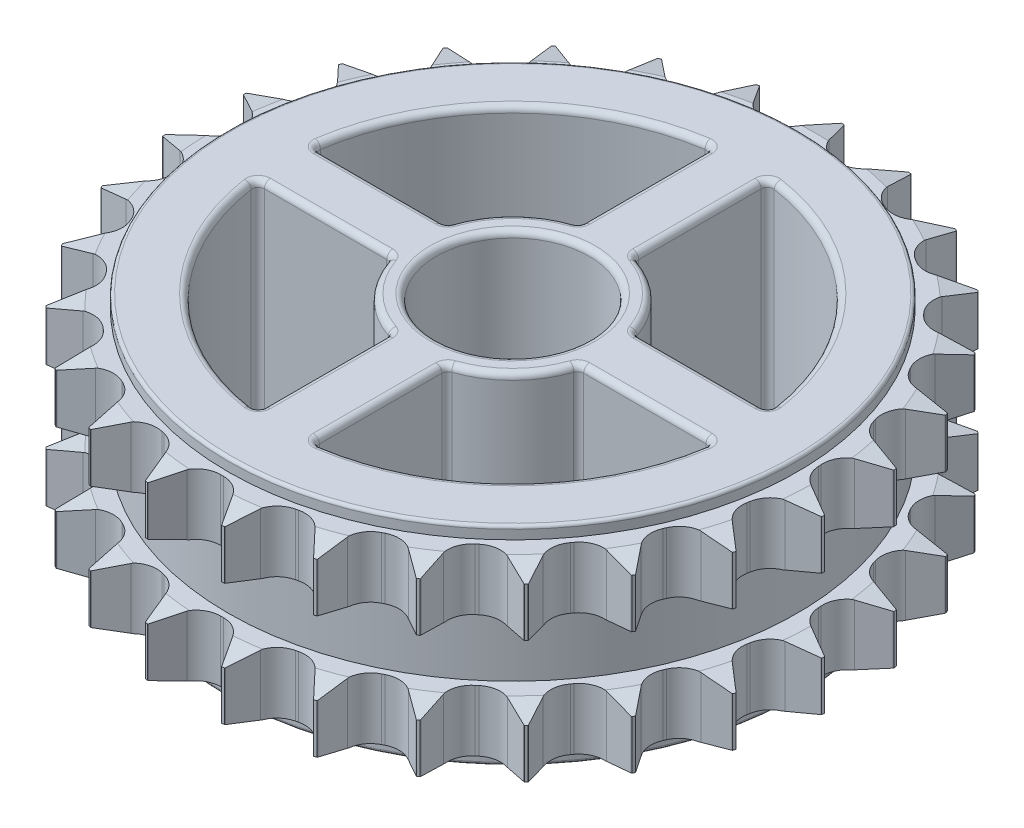
SolidWorks part; units mm, degrees
ref_plane "Front Plane" through (0, 0, 0) normal (0, 0, 1) x (1, 0, 0)
ref_plane "Top Plane" through (0, 0, 0) normal (0, 1, 0) x (1, 0, 0)
ref_plane "Right Plane" through (0, 0, 0) normal (1, 0, 0) x (0, 0, -1)
sketch "Sketch1" plane through (0, 0, 0) normal (0, 1, 0) x (1, 0, 0)
  line L0 (3, 47.4052) -> (0, 54.5)
  line L1 (0, 54.5) -> (-3, 47.4052)
  line L2 (0, 54.5) -> (0, 47.5) construction
  line L3 (-3, 47.4052) -> (0, 47.5) construction
  line L4 (0, 47.5) -> (3, 47.4052) construction
  line L5 (-3, 47.4052) -> (0, 47.5) construction
  line L6 (0, 47.5) -> (3, 47.4052) construction
  line L7 (13.8515, 45.4355) -> (12.5686, 53.0309)
  line L8 (12.5686, 53.0309) -> (8.0132, 46.8192)
  line L9 (23.9563, 41.0164) -> (24.4596, 48.703)
  line L10 (24.4596, 48.703) -> (18.5945, 43.7092)
  line L11 (32.7696, 34.3861) -> (35.0319, 41.7494)
  line L12 (35.0319, 41.7494) -> (28.1733, 38.2428)
  line L13 (39.8163, 25.902) -> (43.7157, 32.5451)
  line L14 (43.7157, 32.5451) -> (36.2333, 30.7148)
  line L15 (44.7164, 16.0216) -> (50.0428, 21.5863)
  line L16 (50.0428, 21.5863) -> (42.3399, 21.5309)
  line L17 (47.2059, 5.2774) -> (53.672, 9.4638)
  line L18 (53.672, 9.4638) -> (46.164, 11.1862)
  line L19 (47.1505, -5.7513) -> (54.4078, -3.1689)
  line L20 (54.4078, -3.1689) -> (47.4994, 0.2386)
  line L21 (44.5532, -16.4699) -> (52.2104, -15.6308)
  line L22 (52.2104, -15.6308) -> (46.2741, -10.722)
  line L23 (39.5541, -26.3007) -> (47.1984, -27.25)
  line L24 (47.1984, -27.25) -> (42.5541, -21.1045)
  line L25 (32.4225, -34.7135) -> (39.6419, -37.4002)
  line L26 (39.6419, -37.4002) -> (36.54, -30.3493)
  line L27 (23.5431, -41.255) -> (29.9482, -45.5341)
  line L28 (29.9482, -45.5341) -> (28.556, -37.9579)
  line L29 (13.3944, -45.5723) -> (18.6401, -51.2132)
  line L30 (18.6401, -51.2132) -> (19.0326, -43.5202)
  line L31 (2.5237, -47.4329) -> (6.3271, -54.1315)
  line L32 (6.3271, -54.1315) -> (8.4831, -46.7364)
  line L33 (-8.4831, -46.7364) -> (-6.3271, -54.1315)
  line L34 (-6.3271, -54.1315) -> (-2.5237, -47.4329)
  line L35 (-19.0326, -43.5202) -> (-18.6401, -51.2132)
  line L36 (-18.6401, -51.2132) -> (-13.3944, -45.5723)
  line L37 (-28.556, -37.9579) -> (-29.9482, -45.5341)
  line L38 (-29.9482, -45.5341) -> (-23.5431, -41.255)
  line L39 (-36.54, -30.3493) -> (-39.6419, -37.4002)
  line L40 (-39.6419, -37.4002) -> (-32.4225, -34.7135)
  line L41 (-42.5541, -21.1045) -> (-47.1984, -27.25)
  line L42 (-47.1984, -27.25) -> (-39.5541, -26.3007)
  line L43 (-46.2741, -10.722) -> (-52.2104, -15.6308)
  line L44 (-52.2104, -15.6308) -> (-44.5532, -16.4699)
  line L45 (-47.4994, 0.2386) -> (-54.4078, -3.1689)
  line L46 (-54.4078, -3.1689) -> (-47.1505, -5.7513)
  line L47 (-46.164, 11.1862) -> (-53.672, 9.4638)
  line L48 (-53.672, 9.4638) -> (-47.2059, 5.2774)
  line L49 (-42.3399, 21.5309) -> (-50.0428, 21.5863)
  line L50 (-50.0428, 21.5863) -> (-44.7164, 16.0216)
  line L51 (-36.2333, 30.7148) -> (-43.7157, 32.5451)
  line L52 (-43.7157, 32.5451) -> (-39.8163, 25.902)
  line L53 (-28.1733, 38.2428) -> (-35.0319, 41.7494)
  line L54 (-35.0319, 41.7494) -> (-32.7696, 34.3861)
  line L55 (-18.5945, 43.7092) -> (-24.4596, 48.703)
  line L56 (-24.4596, 48.703) -> (-23.9563, 41.0164)
  line L57 (-8.0132, 46.8192) -> (-12.5686, 53.0309)
  line L58 (-12.5686, 53.0309) -> (-13.8515, 45.4355)
  line L59 (0, 16) -> (0, 37.5) construction
  line L60 (-4.5, 37.229) -> (-4.5, 15.3542)
  line L61 (4.5, 37.229) -> (4.5, 15.3542)
  line L62 (37.229, -4.5) -> (15.3542, -4.5)
  line L63 (37.229, 4.5) -> (15.3542, 4.5)
  line L64 (-4.5, -37.229) -> (-4.5, -15.3542)
  line L65 (4.5, -37.229) -> (4.5, -15.3542)
  line L66 (-37.229, 4.5) -> (-15.3542, 4.5)
  line L67 (-37.229, -4.5) -> (-15.3542, -4.5)
  line L69 (-1.7, 1.3964) -> (-1.7, -1.3964)
  circle A0 centre (0, 0) radius 47.5
  circle A1 centre (0, 0) radius 37.5
  circle A2 centre (0, 0) radius 5
  circle A3 centre (0, 0) radius 2.2
  circle A4 centre (0, 0) radius 16
  circle A5 centre (0, 0) radius 46.5
  point P88 (0, 0)
  point P111 (0, 0)
  dimension "D1" = 95
  dimension "D5" = 75
  dimension "D6" = 10
  dimension "D7" = 4.4
  dimension "D8" = 32
  dimension "D9" = 4
  dimension "D11" = 0.5
  dimension "D12" = 1
  dimension "D2" = 7
  dimension "D3" = 3
  dimension "D10" = 9
  dimension "D4" = 27
extrude "Boss-Extrude2" add sketch "Sketch1" along normal blind 10 from offset 2 contours A2 A3 | L69 A3 | A4 A2 | A4 L62 A1 L63 | A4 L64 A1 L65 | A4 L66 A1 L67 | A4 L61 A1 L60 | A5 A1 | A0 | L69 A3 region at (5.4988, 0, -47.0454) region at (0, 0, -26.5974) region at (0, 0, -15.5475) region at (-26.5974, 0, 0) region at (26.5974, 0, 0) region at (0, 0, 26.5974) region at (0.1274, 0, 0) region at (-1.9021, 0, 0) region at (-4.8586, 0, 0) region at (-45.1848, 0, 0)
extrude "Boss-Extrude3" add sketch "Sketch1<7>" along normal blind 22 contours L69 A3 | A5 A1 | A4 A2 | A2 A3 | A4 L66 A1 L67 | A4 L64 A1 L65 | A4 L62 A1 L63 | A4 L61 A1 L60 | A3 region at (0, 0, -26.5974) region at (0, 0, -15.5475) region at (-26.5974, 0, 0) region at (26.5974, 0, 0) region at (0, 0, 26.5974) region at (-1.9021, 0, 0) region at (-4.8586, 0, 0) region at (-45.1848, 0, 0)
sketch "Sketch1<7>" plane through (0, 0, 0) normal (0, 1, 0) x (1, 0, 0) same geometry as "Sketch1"
extrude "Boss-Extrude4" add sketch "Sketch1<8>" along normal blind 10 from surface contours A4 A2 | A2 A3 | L69 A3 | A4 L62 A1 L63 | A4 L64 A1 L65 | A4 L66 A1 L67 | A4 L61 A1 L60 | A5 A1 | A0 region at (5.4988, 0, -47.0454) region at (0, 0, -26.5974) region at (0, 0, -15.5475) region at (-26.5974, 0, 0) region at (26.5974, 0, 0) region at (0, 0, 26.5974) region at (-1.9021, 0, 0) region at (-4.8586, 0, 0) region at (-45.1848, 0, 0) starting at face at (-17.1554, 22, 17.1554)
sketch "Sketch1<8>" plane through (0, 0, 0) normal (0, 1, 0) x (1, 0, 0) same geometry as "Sketch1"
extrude "Boss-Extrude6" add sketch "Sketch1<10>" along normal blind 10 from offset 2 contours A0 L57 L58 region at (-11.4875, 0, -48.4696)
sketch "Sketch1<10>" plane through (0, 0, 0) normal (0, 1, 0) x (1, 0, 0) same geometry as "Sketch1"
extrude "Boss-Extrude7" add sketch "Sketch1<12>" along normal blind 10 from surface contours A0 L57 L58 region at (-11.4875, 0, -48.4696) starting at face at (0, 22, 47.5)
sketch "Sketch1<12>" plane through (0, 0, 0) normal (0, 1, 0) x (1, 0, 0) same geometry as "Sketch1"
fillet "Fillet1" radius 4 4 edges at (-13.8515, 7, -45.4355) (-8.0132, 7, -46.8192) (-13.8515, 27, -45.4355) (-8.0132, 27, -46.8192)
fillet "Fillet2" radius 0.3 2 edges at (-12.5686, 7, -53.0309) (-12.5686, 27, -53.0309)
pattern_circular "CirPattern1" count 27 over 360 about axis through (0, 32, 0) along (0, 1, 0) of "Fillet2", "Fillet1", "Boss-Extrude7", "Boss-Extrude6"
sketch "Sketch3" plane through (0, 32, 0) normal (0, 1, 0) x (1, 0, 0)
  circle A0 centre (0, 0) radius 2.5
sketch "Sketch4" plane through (0, 32, 0) normal (0, 1, 0) x (1, 0, 0)
  circle A0 centre (0, 0) radius 0.5
  dimension "D1" = 1
sketch "Sketch6" plane through (0, 32, 0) normal (0, 1, 0) x (1, 0, 0)
  line L0 (-15.3542, 4.5) -> (-37.229, 4.5)
  line L1 (-15.3542, -4.5) -> (-37.229, -4.5)
  line L2 (4.5, 15.3542) -> (4.5, 37.229)
  line L3 (-4.5, 15.3542) -> (-4.5, 37.229)
  line L4 (15.3542, -4.5) -> (37.229, -4.5)
  line L5 (15.3542, 4.5) -> (37.229, 4.5)
  line L6 (-4.5, -15.3542) -> (-4.5, -37.229)
  line L7 (4.5, -15.3542) -> (4.5, -37.229)
  circle A0 centre (0, 0) radius 16
  circle A1 centre (0, 0) radius 46.5
  circle A2 centre (0, 0) radius 37.5
  circle A3 centre (0, 0) radius 16
  circle A4 centre (0, 0) radius 16
  circle A5 centre (0, 0) radius 16
  point P31 (0, 0)
  dimension "D1" = 93
  dimension "D2" = 32
  dimension "D3" = 4
extrude "Boss-Extrude12" add sketch "Sketch6" along normal blind 2 contours L2 A2 L3 A0 | A1 A2 | L0 A2 L1 A0 | L6 A2 L7 A0 | A0 | L4 A2 L5 A0 region at (-26.5974, 32, 0) region at (0, 32, 0) region at (0, 32, -26.5974) region at (0, 32, 26.5974) region at (26.5974, 32, 0) region at (-45.1848, 32, 0)
fillet "Fillet9" radius 0.5 2 edges at (0, 34, 46.5) (0, 0, 46.5)
sketch "Sketch7" plane through (0, 34, 0) normal (0, 1, 0) x (1, 0, 0)
  line L0 (0, 0) -> (0, 5.8384) construction
  line L1 (0, 0) -> (-4.8311, 0) construction
  circle A1 centre (-8, 0) radius 1.5
  circle A2 centre (0, 8) radius 1.5
  circle A3 centre (8, 0) radius 1.5
  circle A4 centre (0, -8) radius 1.5
  point P3 (0, 0)
  point P18 (0, 0)
  dimension "D2" = 3
  dimension "D1" = 90
  dimension "D3" = 8
  dimension "D4" = 4
extrude "Cut-Extrude1" cut sketch "Sketch7" against normal up to next
sketch "Sketch10" plane through (0, 34, 0) normal (0, 1, 0) x (1, 0, 0)
  circle A0 centre (0, 0) radius 12.5
  dimension "D1" = 25
extrude "Cut-Extrude2" cut sketch "Sketch10" against normal offset from surface (21 mm away) 13 up to face at (-8, 0, 1.5)
fillet "Fillet17" radius 1 44 edges at (15.3542, 17, -4.5) (37.229, 17, -4.5) (-4.5, 17, 37.229) (-4.5, 17, 15.3542) (-15.3542, 17, 4.5) (-37.229, 17, 4.5) (-37.229, 17, -4.5) (-15.3542, 17, -4.5) (-4.5, 17, -15.3542) (-4.5, 17, -37.229) (4.5, 17, -37.229) (4.5, 17, -15.3542) (4.5, 17, 15.3542) (4.5, 17, 37.229) (37.229, 17, 4.5) (15.3542, 17, 4.5) (-11.3137, 34, 11.3137) (-26.5165, 34, -26.5165) (-11.3137, 0, 11.3137) (26.5165, 0, 26.5165) (-11.3137, 34, -11.3137) (-11.3137, 0, -11.3137) (11.3137, 34, -11.3137) (26.5165, 34, -26.5165) (11.3137, 0, -11.3137) (11.3137, 34, 11.3137) (11.3137, 0, 11.3137) (26.2916, 34, -4.5) (26.2916, 0, -4.5) (-4.5, 34, 26.2916) (-4.5, 0, 26.2916) (-26.2916, 34, 4.5) (-26.2916, 0, 4.5) (-26.2916, 34, -4.5) (-26.2916, 0, -4.5) (-4.5, 34, -26.2916) (-4.5, 0, -26.2916) (4.5, 34, -26.2916) (4.5, 0, -26.2916) (4.5, 34, 26.2916) (4.5, 0, 26.2916) (26.2916, 34, 4.5) (26.2916, 0, 4.5) (0, 34, 12.5)
sketch "Sketch11" plane through (0, 0, 0) normal (0, 0, 1) x (1, 0, 0)
  line L0 (-49.4165, 12) -> (-53.7394, 12) construction
  line L1 (-53.7394, 2) -> (-49.4165, 2) construction
  line L2 (-49.4165, 2) -> (-49.4165, 12) construction
  line L3 (-53.7394, 12) -> (-53.9388, 12) construction
  line L4 (-53.7715, 12) -> (-53.7715, 2) construction
  line L5 (-53.9388, 2) -> (-53.7394, 2) construction
  line L6 (-53.7394, 32) -> (-53.9388, 32) construction
  line L7 (-53.7715, 32) -> (-53.7715, 22) construction
  line L8 (-53.9388, 22) -> (-53.7394, 22) construction
  line L9 (-49.4165, 32) -> (-53.7394, 32) construction
  line L10 (-53.7394, 22) -> (-49.4165, 22) construction
  line L11 (-49.4165, 22) -> (-49.4165, 32) construction
  line L13 (-49.4165, 12) -> (-53.7394, 12)
  line L14 (-53.7394, 2) -> (-49.4165, 2)
  line L15 (-49.4165, 2) -> (-49.4165, 12)
  line L16 (-53.7394, 12) -> (-53.9388, 12)
  line L17 (-53.7715, 12) -> (-53.7715, 2)
  line L18 (-53.9388, 2) -> (-53.7394, 2)
  line L19 (-53.7394, 32) -> (-53.9388, 32)
  line L20 (-53.7715, 32) -> (-53.7715, 22)
  line L21 (-53.9388, 22) -> (-53.7394, 22)
  line L22 (-49.4165, 32) -> (-53.7394, 32)
  line L23 (-53.7394, 22) -> (-49.4165, 22)
  line L24 (-49.4165, 22) -> (-49.4165, 32)
  line L25 (-53.9388, 32) -> (-53.9388, 22)
  line L26 (-53.9388, 12) -> (-53.9388, 2) construction
  line L27 (-53.9388, 12) -> (-53.9388, 2)
  line L28 (-53.9388, 22) -> (-53.9388, 12) construction
  line L29 (-53.9388, 17) -> (-47.598, 17) construction
  line L30 (-52.955, 27) -> (-56.5762, 27) construction
  line L31 (-49.4165, 32) -> (-53.9388, 31)
  line L32 (-49.4165, 22) -> (-53.9388, 23)
  line L33 (-49.4165, 12) -> (-53.9388, 11)
  line L34 (-49.4165, 2) -> (-53.9388, 3)
  line L35 (0, 27) -> (0, 33.2542) construction
  line L36 (-53.9388, 32) -> (-54.2683, 32)
  line L37 (-53.9388, 31) -> (-54.2683, 31)
  line L38 (-53.9388, 31) -> (-53.9388, 23)
  line L39 (-53.9388, 23) -> (-54.2683, 23)
  line L40 (-54.2683, 31) -> (-54.2683, 23)
  line L41 (-54.2683, 32) -> (-54.2683, 31)
  line L42 (-54.2683, 23) -> (-54.2683, 22)
  line L43 (-54.2683, 22) -> (-53.9388, 22)
  line L45 (-53.9388, 12) -> (-54.2683, 12)
  line L46 (-53.9388, 12) -> (-53.9388, 2)
  line L47 (-53.9388, 2) -> (-54.2683, 2)
  line L48 (-54.2683, 12) -> (-54.2683, 2)
  point P7 (-53.9388, 17)
  point P20 (-53.9388, 27)
  dimension "D1" = 1
revolve "Cut-Revolve1" cut sketch "Sketch11" angle 360 about L35 region at (-52.3198, 11.679, 0) region at (-52.3198, 2.321, 0) region at (-53.8557, 11.5092, 0) region at (-53.8557, 2.4908, 0) region at (-54.1035, 7, 0) region at (-52.3198, 31.679, 0) region at (-53.8557, 31.5092, 0) region at (-54.1035, 31.5, 0) region at (-52.3198, 22.321, 0) region at (-54.1035, 27, 0) region at (-53.8557, 22.4908, 0) region at (-54.1035, 22.5, 0)
